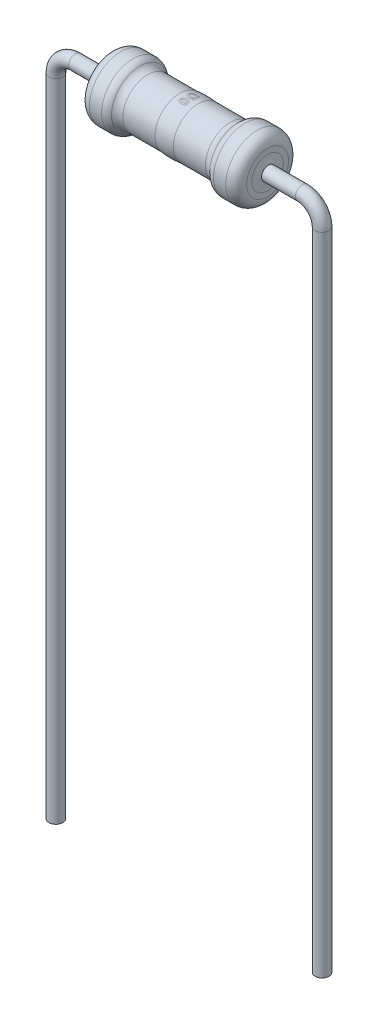
SolidWorks part; units mm, degrees
material "Plain Carbon Steel"
ref_plane "Front Plane" through (0, 0, 0) normal (0, 0, 1) x (1, 0, 0)
ref_plane "Top Plane" through (0, 0, 0) normal (0, 1, 0) x (1, 0, 0)
ref_plane "Right Plane" through (0, 0, 0) normal (1, 0, 0) x (0, 0, -1)
sketch "Sketch1" plane through (0, 0, 0) normal (0, 0, 1) x (1, 0, 0)
  line L0 (-4.33, 0) -> (4.33, 0)
  line L1 (-5.08, -0.75) -> (-5.08, -25.4)
  line L2 (5.08, -0.75) -> (5.08, -25.4)
  line L3 (-5.08, -25.4) -> (5.08, -25.4) construction
  line L4 (0, 0) -> (0, -25.4) construction
  arc A0 (-4.33, 0) -> (-5.08, -0.75) centre (-4.33, -0.75) ccw
  arc A1 (4.33, 0) -> (5.08, -0.75) centre (4.33, -0.75) cw
  dimension "D2" = 0.75
  dimension "D1" = 10.16
  dimension "D3" = 25.4
ref_plane "Plane1" through (-5.08, -25.4, 0) normal (0, -1, 0) x (-1, 0, 0)
sketch "Sketch2" plane through (-5.08, -25.4, 0) normal (0, -1, 0) x (-1, 0, 0)
  circle A0 centre (0, 0) radius 0.265
  dimension "D1" = 0.53
sweep "Sweep1" add profiles "Sketch2" path "Sketch1"
sketch "Sketch3" plane through (0, 0, 0) normal (0, 0, 1) x (1, 0, 0)
  line L0 (-3, 0) -> (3, 0)
  line L5 (-3, 0) -> (-3, 1.2)
  line L6 (3, 0) -> (3, 1.2)
  line L7 (-3, 1.2) -> (-1.8, 1.2)
  line L8 (3, 1.2) -> (1.8, 1.2)
  line L9 (-1.8, 1.2) -> (-1.8, 0.95)
  line L10 (-1.8, 0.95) -> (1.8, 0.95)
  line L11 (1.8, 0.95) -> (1.8, 1.2)
  line L12 (0, 0) -> (0, 0.95) construction
  dimension "D1" = 6
  dimension "D2" = 1.2
  dimension "D3" = 3.6
  dimension "D4" = 0.95
  dimension "D5" = 0.25
revolve "Revolve1" add sketch "Sketch3" angle 360 about L0
fillet "Fillet-1" radius 0.35 2 edges at (1.8, 0, 1.2) (-1.8, 0, 1.2)
fillet "Fillet-2" radius 0.4 4 edges at (3, 0, 1.2) (-3, 0, 1.2) (1.8, 0, 0.95) (-1.8, 0, 0.95)
sketch "Sketch5" plane through (0, 0, 0) normal (0, 0, 1) x (1, 0, 0)
  line L0 (-0.35, 0) -> (0.35, 0)
  line L5 (0, 0) -> (0, 0.95) construction
  line L10 (-0.35, 0.95) -> (0.35, 0.95) construction
  line L15 (-0.35, 0.95) -> (-0.35, 0)
  line L30 (1.5764, 0.95) -> (-1.5764, 0.95) construction
  line L39 (0.35, 0.95) -> (0.35, 0)
  line L41 (0, 0.95) -> (0, 0.97) construction
  line L48 (-3, 0) -> (-3, 0.6)
  line L49 (-3, 0) -> (-3, 1.2) construction
  line L50 (-3, 0) -> (-3.05, 0)
  line L51 (-3.05, 0) -> (-3.05, 0.2)
  line L52 (3, 0) -> (3.05, 0)
  line L53 (3.05, 0) -> (3.05, 0.2)
  line L54 (3, 0) -> (3, 0.6)
  line L55 (3, 0) -> (3, 1.2) construction
  arc A6 (-3, 0.6) -> (-3.05, 0.2) centre (-4.625, 0.6) cw
  arc A7 (3.05, 0.2) -> (3, 0.6) centre (4.625, 0.6) cw
  arc A8 (-0.35, 0.95) -> (0.35, 0.95) centre (0, -2.1025) cw
  dimension "D5" = 0.05
  dimension "D7" = 0.6
  dimension "D8" = 0.7
  dimension "D9" = 0.02
  dimension "D6" = 0.2
revolve "Revolve2" add sketch "Sketch5" angle 360 about L0
ref_plane "Plane2" through (0, 2, 0) normal (0, 1, 0) x (1, 0, 0)
sketch "Sketch6" plane through (0, 2, 0) normal (0, 1, 0) x (1, 0, 0)
  line L0 (-0.35, 0) -> (0.15, 0) construction
  line L1 (0.15, 0.75) -> (0.15, -0.75) construction
  line L3 (-0.35, 0.95) -> (-0.35, -0.95) construction
  text T0 "0Ω" font "Calibri" height 0.3
  dimension "D1" = 0.5
  dimension "D2" = 1.5
wrap "Wrap1" sketch "Sketch6" wrap type scribe source sketch "Sketch6" face at (-0.35, 0, -0.95)
